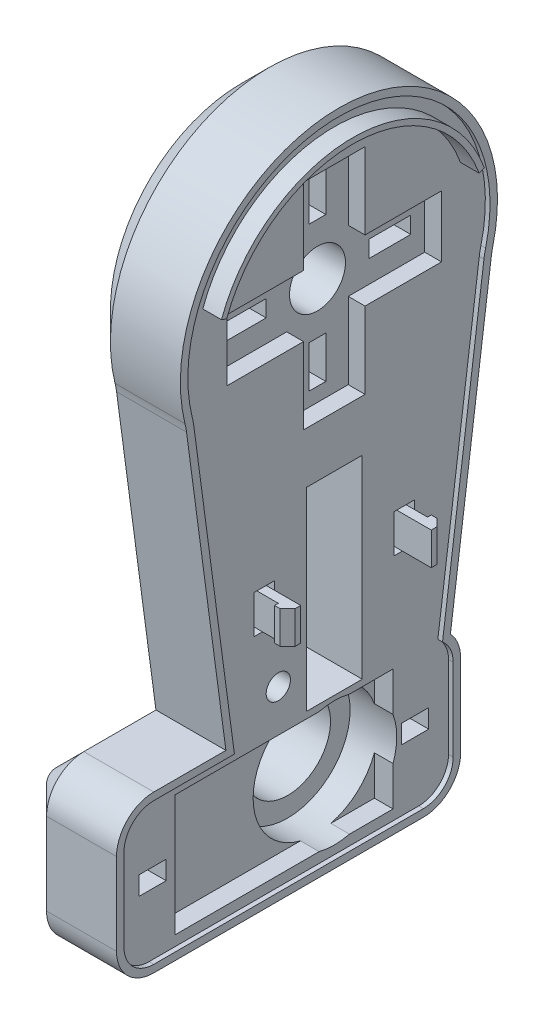
SolidWorks part; units mm, degrees
ref_plane "Front Plane" through (0, 0, 0) normal (0, 0, 1) x (1, 0, 0)
ref_plane "Top Plane" through (0, 0, 0) normal (0, 1, 0) x (1, 0, 0)
ref_plane "Right Plane" through (0, 0, 0) normal (1, 0, 0) x (0, 0, -1)
sketch "Sketch1" plane through (0, 0, 0) normal (1, 0, 0) x (0, 0, -1)
  line L0 (-49.6573, -24.9297) -> (-54.0465, -57.8487)
  line L1 (-52.95, -60.6) -> (-52.95, -69.4)
  line L2 (-56.95, -73.4) -> (-85.85, -73.4)
  line L3 (-89.85, -69.4) -> (-89.85, -60.6)
  line L4 (-85.85, -56.6) -> (-78.12, -56.6)
  line L5 (-78.12, -56.6) -> (-82.3427, -24.9297)
  arc A0 (-82.5053, -24.0712) -> (-49.4947, -24.0712) centre (-66, -20) cw
  arc A1 (-49.4947, -24.0712) -> (-49.6573, -24.9297) centre (-41.7275, -25.987) ccw
  arc A2 (-54.0465, -57.8487) -> (-52.95, -60.6) centre (-56.95, -60.6) cw
  arc A3 (-52.95, -69.4) -> (-56.95, -73.4) centre (-56.95, -69.4) cw
  arc A4 (-85.85, -73.4) -> (-89.85, -69.4) centre (-85.85, -69.4) cw
  arc A5 (-89.85, -60.6) -> (-85.85, -56.6) centre (-85.85, -60.6) cw
  arc A6 (-82.3427, -24.9297) -> (-82.5053, -24.0712) centre (-90.2725, -25.987) ccw
extrude "Boss-Extrude1" add sketch "Sketch1" along normal blind 10.5 from offset 76.4 offset against normal yes
sketch "Sketch2" plane through (0, 0, 0) normal (1, 0, 0) x (0, 0, -1)
  line L0 (-50.4503, -24.824) -> (-54.8935, -58.1483)
  line L1 (-53.75, -60.6) -> (-53.75, -69.4)
  line L2 (-56.95, -72.6) -> (-85.85, -72.6)
  line L3 (-89.05, -69.4) -> (-89.05, -60.6)
  line L4 (-85.85, -57.4) -> (-77.2063, -57.4)
  line L5 (-77.2063, -57.4) -> (-81.5497, -24.824)
  arc A0 (-81.7286, -23.8796) -> (-50.2714, -23.8796) centre (-66, -20) cw
  arc A1 (-50.2714, -23.8796) -> (-50.4503, -24.824) centre (-41.7275, -25.987) ccw
  arc A2 (-54.8935, -58.1483) -> (-53.75, -60.6) centre (-56.95, -60.6) cw
  arc A3 (-53.75, -69.4) -> (-56.95, -72.6) centre (-56.95, -69.4) cw
  arc A4 (-85.85, -72.6) -> (-89.05, -69.4) centre (-85.85, -69.4) cw
  arc A5 (-89.05, -60.6) -> (-85.85, -57.4) centre (-85.85, -60.6) cw
  arc A6 (-81.5497, -24.824) -> (-81.7286, -23.8796) centre (-90.2725, -25.987) ccw
extrude "Boss-Extrude2" add sketch "Sketch2" along normal blind 0.6 from offset 66.4 separate body offset against normal yes
combine bodies "Combine1" operation type subtract main body 101 bodies to subtract 102
chamfer "Chamfer1" distance 3 angle 45 5 edges at (-76.4, -41.3892, 51.8519) (-76.4, -40.7649, 80.2314) (-76.4, -24.4982, 49.5877) (-76.4, -24.4982, 82.4123) (-76.4, -3, 66)
chamfer "Chamfer2" distance 3 angle 45 8 edges at (-76.4, -56.6, 80.4717) (-76.4, -57.7716, 88.6784) (-76.4, -57.787, 54.1063) (-76.4, -65, 89.85) (-76.4, -65, 52.95) (-76.4, -72.2284, 88.6784) (-76.4, -72.2284, 54.1216) (-76.4, -73.4, 71.4)
sketch "Sketch3" plane through (0, 0, 0) normal (0, 0, 1) x (1, 0, 0)
  line L1 (-68.2, -31.5) -> (-65.9, -31.5)
  line L2 (-68.2, -31.5) -> (-68.2, -8.5)
  line L3 (-68.2, -8.5) -> (-65.9, -8.5)
  line L4 (-65.9, -31.5) -> (-65.9, -8.5)
extrude "Boss-Extrude3" add sketch "Sketch3" along normal blind 6.6 from offset 62.7 separate body
combine bodies "Combine2" operation type subtract main body 103 bodies to subtract 104
sketch "Sketch4" plane through (0, 0, 0) normal (0, 0, 1) x (1, 0, 0)
  line L1 (-68.2, -23.3) -> (-65.9, -23.3)
  line L2 (-68.2, -23.3) -> (-68.2, -16.7)
  line L3 (-68.2, -16.7) -> (-65.9, -16.7)
  line L4 (-65.9, -23.3) -> (-65.9, -16.7)
extrude "Boss-Extrude4" add sketch "Sketch4" along normal blind 23 from offset 54.5 separate body
combine bodies "Combine3" operation type subtract main body 105 bodies to subtract 106
sketch "Sketch5" plane through (0, 0, 0) normal (1, 0, 0) x (0, 0, -1)
  circle A0 centre (-66, -20) radius 4.6
extrude "Boss-Extrude5" add sketch "Sketch5" along normal blind 2.3 from offset 68.2 separate body offset against normal yes
combine bodies "Combine4" operation type subtract main body 107 bodies to subtract 108
sketch "Sketch6" plane through (0, 0, 0) normal (1, 0, 0) x (0, 0, -1)
  circle A0 centre (-66, -20) radius 6.1
extrude "Boss-Extrude6" add sketch "Sketch6" along normal blind 1.7 from offset 76.9 separate body offset against normal yes
combine bodies "Combine5" operation type subtract main body 109 bodies to subtract 110
sketch "Sketch7" plane through (0, 0, 0) normal (1, 0, 0) x (0, 0, -1)
  circle A0 centre (-66, -20) radius 3
extrude "Boss-Extrude7" add sketch "Sketch7" along normal blind 7.2 from offset 75.3 separate body offset against normal yes
combine bodies "Combine6" operation type subtract main body 111 bodies to subtract 112
sketch "Sketch8" plane through (0, 0, 0) normal (0, 0, 1) x (1, 0, 0)
  line L1 (-74.2, -14.5) -> (-68.1, -14.5)
  line L2 (-74.2, -14.5) -> (-74.2, -13.4)
  line L3 (-74.2, -13.4) -> (-68.1, -13.4)
  line L4 (-68.1, -14.5) -> (-68.1, -13.4)
extrude "Boss-Extrude8" add sketch "Sketch8" along normal blind 1.8 from offset 65.1 separate body
combine bodies "Combine7" operation type subtract main body 113 bodies to subtract 114
sketch "Sketch9" plane through (0, 0, 0) normal (0, 0, 1) x (1, 0, 0)
  line L1 (-74.2, -20.9) -> (-68.1, -20.9)
  line L2 (-74.2, -20.9) -> (-74.2, -19.1)
  line L3 (-74.2, -19.1) -> (-68.1, -19.1)
  line L4 (-68.1, -20.9) -> (-68.1, -19.1)
extrude "Boss-Extrude9" add sketch "Sketch9" along normal blind 1.1 from offset 71.5 separate body
combine bodies "Combine8" operation type subtract main body 115 bodies to subtract 116
sketch "Sketch10" plane through (0, 0, 0) normal (0, 0, 1) x (1, 0, 0)
  line L1 (-74.2, -26.6) -> (-68.1, -26.6)
  line L2 (-74.2, -26.6) -> (-74.2, -25.5)
  line L3 (-74.2, -25.5) -> (-68.1, -25.5)
  line L4 (-68.1, -26.6) -> (-68.1, -25.5)
extrude "Boss-Extrude10" add sketch "Sketch10" along normal blind 1.8 from offset 65.1 separate body
combine bodies "Combine9" operation type subtract main body 117 bodies to subtract 118
sketch "Sketch11" plane through (0, 0, 0) normal (0, 0, 1) x (1, 0, 0)
  line L1 (-74.2, -20.9) -> (-68.1, -20.9)
  line L2 (-74.2, -20.9) -> (-74.2, -19.1)
  line L3 (-74.2, -19.1) -> (-68.1, -19.1)
  line L4 (-68.1, -20.9) -> (-68.1, -19.1)
extrude "Boss-Extrude11" add sketch "Sketch11" along normal blind 1.1 from offset 59.4 separate body
combine bodies "Combine10" operation type subtract main body 119 bodies to subtract 120
sketch "Sketch12" plane through (0, 0, 0) normal (0, 0, 1) x (1, 0, 0)
  line L1 (-75.4, -13.4) -> (-68.1, -13.4)
  line L2 (-75.4, -13.4) -> (-75.4, -10)
  line L3 (-75.4, -10) -> (-68.1, -10)
  line L4 (-68.1, -13.4) -> (-68.1, -10)
extrude "Boss-Extrude12" add sketch "Sketch12" along normal blind 1.8 from offset 65.1 separate body
combine bodies "Combine11" operation type subtract main body 121 bodies to subtract 122
sketch "Sketch13" plane through (0, 0, 0) normal (0, 0, 1) x (1, 0, 0)
  line L1 (-75.4, -20.9) -> (-68.1, -20.9)
  line L2 (-75.4, -20.9) -> (-75.4, -19.1)
  line L3 (-75.4, -19.1) -> (-68.1, -19.1)
  line L4 (-68.1, -20.9) -> (-68.1, -19.1)
extrude "Boss-Extrude13" add sketch "Sketch13" along normal blind 3.4 from offset 72.6 separate body
combine bodies "Combine12" operation type subtract main body 123 bodies to subtract 124
sketch "Sketch14" plane through (0, 0, 0) normal (0, 0, 1) x (1, 0, 0)
  line L1 (-75.4, -30) -> (-68.1, -30)
  line L2 (-75.4, -30) -> (-75.4, -26.6)
  line L3 (-75.4, -26.6) -> (-68.1, -26.6)
  line L4 (-68.1, -30) -> (-68.1, -26.6)
extrude "Boss-Extrude14" add sketch "Sketch14" along normal blind 1.8 from offset 65.1 separate body
combine bodies "Combine13" operation type subtract main body 125 bodies to subtract 126
sketch "Sketch15" plane through (0, 0, 0) normal (0, 0, 1) x (1, 0, 0)
  line L1 (-75.4, -20.9) -> (-68.1, -20.9)
  line L2 (-75.4, -20.9) -> (-75.4, -19.1)
  line L3 (-75.4, -19.1) -> (-68.1, -19.1)
  line L4 (-68.1, -20.9) -> (-68.1, -19.1)
extrude "Boss-Extrude15" add sketch "Sketch15" along normal blind 3.4 from offset 56 separate body
combine bodies "Combine14" operation type subtract main body 127 bodies to subtract 128
sketch "Sketch16" plane through (0, 0, 0) normal (1, 0, 0) x (0, 0, -1)
  line L0 (-51.9046, -14.8697) -> (-52.4684, -15.0749)
  line L1 (-79.5316, -15.0749) -> (-80.0954, -14.8697)
  arc A0 (-80.0954, -14.8697) -> (-51.9046, -14.8697) centre (-66, -20) cw
  arc A1 (-52.4684, -15.0749) -> (-79.5316, -15.0749) centre (-66, -20) ccw
extrude "Boss-Extrude16" add sketch "Sketch16" along normal blind 2.05 from offset 66.45 offset against normal yes
sketch "Sketch17" plane through (0, 0, 0) normal (0, 0, 1) x (1, 0, 0)
  line L1 (-70.4, -66) -> (-66.3, -66)
  line L2 (-70.4, -66) -> (-70.4, -64)
  line L3 (-70.4, -64) -> (-66.3, -64)
  line L4 (-66.3, -66) -> (-66.3, -64)
extrude "Boss-Extrude17" add sketch "Sketch17" along normal blind 2.9 from offset 55.875 separate body
combine bodies "Combine15" operation type subtract main body 130 bodies to subtract 131
sketch "Sketch18" plane through (0, 0, 0) normal (0, 0, 1) x (1, 0, 0)
  line L1 (-70.4, -66) -> (-66.3, -66)
  line L2 (-70.4, -66) -> (-70.4, -64)
  line L3 (-70.4, -64) -> (-66.3, -64)
  line L4 (-66.3, -66) -> (-66.3, -64)
extrude "Boss-Extrude18" add sketch "Sketch18" along normal blind 2.9 from offset 84.025 separate body
combine bodies "Combine16" operation type subtract main body 132 bodies to subtract 133
sketch "Sketch19" plane through (0, 0, 0) normal (0, 0, 1) x (1, 0, 0)
  line L1 (-68.4, -71.5) -> (-66.3, -71.5)
  line L2 (-68.4, -71.5) -> (-68.4, -58.5)
  line L3 (-68.4, -58.5) -> (-66.3, -58.5)
  line L4 (-66.3, -71.5) -> (-66.3, -58.5)
extrude "Boss-Extrude19" add sketch "Sketch19" along normal blind 23.4 from offset 59.7 separate body
combine bodies "Combine17" operation type subtract main body 134 bodies to subtract 135
sketch "Sketch20" plane through (0, 0, 0) normal (1, 0, 0) x (0, 0, -1)
  circle A0 centre (-66, -65) radius 6.7
extrude "Boss-Extrude20" add sketch "Sketch20" along normal blind 5.1 from offset 71.4 separate body offset against normal yes
combine bodies "Combine18" operation type subtract main body 136 bodies to subtract 137
sketch "Sketch21" plane through (0, 0, 0) normal (1, 0, 0) x (0, 0, -1)
  circle A0 centre (-66, -65) radius 4.6
extrude "Boss-Extrude21" add sketch "Sketch21" along normal blind 5.8 from offset 76.9 separate body offset against normal yes
combine bodies "Combine19" operation type subtract main body 138 bodies to subtract 139
sketch "Sketch22" plane through (0, 0, 0) normal (0, 0, 1) x (1, 0, 0)
  line L1 (-74.6, -57.8) -> (-66.3, -57.8)
  line L2 (-74.6, -57.8) -> (-74.6, -37)
  line L3 (-74.6, -37) -> (-66.3, -37)
  line L4 (-66.3, -57.8) -> (-66.3, -37)
extrude "Boss-Extrude22" add sketch "Sketch22" along normal blind 6 from offset 63 separate body
combine bodies "Combine20" operation type subtract main body 140 bodies to subtract 141
sketch "Sketch23" plane through (0, 0, 0) normal (1, 0, 0) x (0, 0, -1)
  circle A0 centre (-72, -54) radius 2.3
extrude "Boss-Extrude23" add sketch "Sketch23" along normal blind 6 from offset 76.9 separate body offset against normal yes
combine bodies "Combine21" operation type subtract main body 142 bodies to subtract 143
sketch "Sketch24" plane through (0, 0, 0) normal (1, 0, 0) x (0, 0, -1)
  circle A0 centre (-72, -54) radius 1.3
extrude "Boss-Extrude24" add sketch "Sketch24" along normal blind 4.65 from offset 70.95 separate body offset against normal yes
combine bodies "Combine22" operation type subtract main body 144 bodies to subtract 145
sketch "Sketch25" plane through (0, 0, 0) normal (0, 0, 1) x (1, 0, 0)
  line L1 (-70.4, -48.05) -> (-66.3, -48.05)
  line L2 (-70.4, -48.05) -> (-70.4, -43.95)
  line L3 (-70.4, -43.95) -> (-66.3, -43.95)
  line L4 (-66.3, -48.05) -> (-66.3, -43.95)
extrude "Boss-Extrude25" add sketch "Sketch25" along normal blind 2.2 from offset 57.4 separate body
combine bodies "Combine23" operation type subtract main body 146 bodies to subtract 147
sketch "Sketch26" plane through (0, 0, 0) normal (0, 1, 0) x (1, 0, 0)
  line L0 (-70.6, -59) -> (-70.6, -58)
  line L1 (-70.6, -58) -> (-64.4, -58)
  line L2 (-64.4, -58) -> (-64.4, -57.6)
  line L3 (-64.4, -57.6) -> (-63.8, -57.6)
  line L4 (-63.8, -57.6) -> (-63, -58.4)
  line L5 (-63, -58.4) -> (-63, -59)
  line L6 (-63, -59) -> (-70.6, -59)
extrude "Boss-Extrude26" add sketch "Sketch26" along normal blind 3.5 from offset 47.75 offset against normal yes
sketch "Sketch27" plane through (0, 0, 0) normal (0, 0, 1) x (1, 0, 0)
  line L1 (-70.4, -48.05) -> (-66.3, -48.05)
  line L2 (-70.4, -48.05) -> (-70.4, -43.95)
  line L3 (-70.4, -43.95) -> (-66.3, -43.95)
  line L4 (-66.3, -48.05) -> (-66.3, -43.95)
extrude "Boss-Extrude27" add sketch "Sketch27" along normal blind 2.2 from offset 72.4 separate body
combine bodies "Combine24" operation type subtract main body 149 bodies to subtract 150
sketch "Sketch28" plane through (0, 0, 0) normal (0, 1, 0) x (1, 0, 0)
  line L0 (-70.6, -73) -> (-70.6, -74)
  line L1 (-70.6, -74) -> (-64.4, -74)
  line L2 (-64.4, -74) -> (-64.4, -74.4)
  line L3 (-64.4, -74.4) -> (-63.8, -74.4)
  line L4 (-63.8, -74.4) -> (-63, -73.6)
  line L5 (-63, -73.6) -> (-63, -73)
  line L6 (-63, -73) -> (-70.6, -73)
extrude "Boss-Extrude28" add sketch "Sketch28" along normal blind 3.5 from offset 47.75 offset against normal yes
